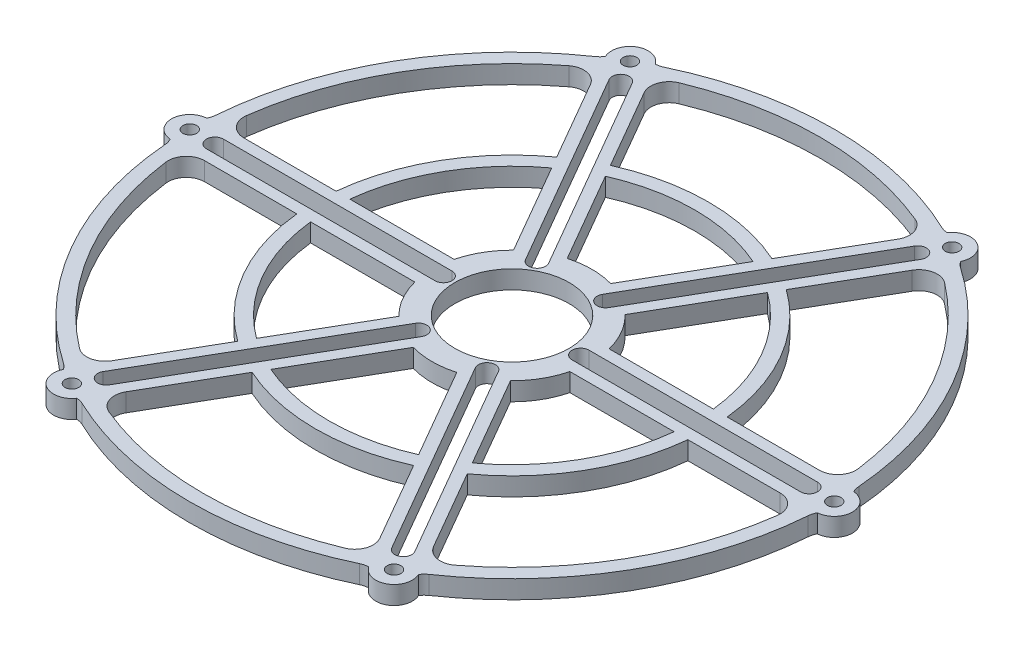
SolidWorks part; units mm, degrees
ref_plane "前视基准面" through (0, 0, 0) normal (0, 0, 1) x (1, 0, 0)
ref_plane "上视基准面" through (0, 0, 0) normal (0, 1, 0) x (1, 0, 0)
ref_plane "右视基准面" through (0, 0, 0) normal (1, 0, 0) x (0, 0, -1)
sketch "草图1" plane through (0, 0, 0) normal (0, 1, 0) x (1, 0, 0)
  line L12 (-35.25, -61.0548) -> (0, 0) construction
  line L13 (-67.3629, 4.3002) -> (-9.579, 4.3002)
  line L14 (-67.3629, -4.3002) -> (-9.579, -4.3002)
  line L15 (9.579, 4.3002) -> (67.3629, 4.3002)
  line L16 (9.579, -4.3002) -> (67.3629, -4.3002)
  line L17 (1.0654, -10.4458) -> (29.9573, -60.4881)
  line L18 (8.5136, -6.1456) -> (37.4056, -56.1878)
  line L19 (-29.9573, 60.4881) -> (-1.0654, 10.4458)
  line L20 (-37.4056, 56.1878) -> (-8.5136, 6.1456)
  line L21 (-8.5136, -6.1456) -> (-37.4056, -56.1878)
  line L22 (-1.0654, -10.4458) -> (-29.9573, -60.4881)
  line L23 (37.4056, 56.1878) -> (8.5136, 6.1456)
  line L24 (29.9573, 60.4881) -> (1.0654, 10.4458)
  line L25 (-9.579, 4.3002) -> (-67.3629, 4.3002)
  line L26 (-9.579, -4.3002) -> (-67.3629, -4.3002)
  line L27 (67.3629, -4.3002) -> (9.579, -4.3002)
  line L28 (67.3629, 4.3002) -> (9.579, 4.3002)
  line L29 (-1.0654, 10.4458) -> (-29.9573, 60.4881)
  line L30 (-8.5136, 6.1456) -> (-37.4056, 56.1878)
  line L31 (29.9573, -60.4881) -> (1.0654, -10.4458)
  line L32 (37.4056, -56.1878) -> (8.5136, -6.1456)
  line L33 (8.5136, 6.1456) -> (37.4056, 56.1878)
  line L34 (1.0654, 10.4458) -> (29.9573, 60.4881)
  line L35 (-37.4056, -56.1878) -> (-8.5136, -6.1456)
  line L36 (-29.9573, -60.4881) -> (-1.0654, -10.4458)
  line L37 (10.5, 0) -> (70.5, 0) construction
  line L38 (-10.5, 0) -> (9.5, 0) construction
  arc A0 (-7.8594, 1.4934) -> (-7.8594, -1.4934) centre (0, 0) ccw construction
  circle A1 centre (-8, 0) radius 1.5
  circle A2 centre (0, 8) radius 1.5
  circle A3 centre (8, 0) radius 1.5
  circle A4 centre (0, -8) radius 1.5
  arc A5 (-8.5136, 6.1456) -> (-9.579, 4.3002) centre (0, 0) ccw
  arc A6 (-67.3629, -4.3002) -> (-37.4056, -56.1878) centre (0, 0) ccw
  arc A7 (-70.5, 3) -> (-70.5, -3) centre (-70.5, 0) ccw
  circle A8 centre (-70.5, 0) radius 1.5
  arc A9 (-32.6519, 62.5548) -> (-37.8481, 59.5548) centre (-35.25, 61.0548) ccw
  circle A10 centre (-35.25, 61.0548) radius 1.5
  arc A11 (37.8481, 59.5548) -> (32.6519, 62.5548) centre (35.25, 61.0548) ccw
  circle A12 centre (35.25, 61.0548) radius 1.5
  arc A13 (70.5, -3) -> (70.5, 3) centre (70.5, 0) ccw
  circle A14 centre (70.5, 0) radius 1.5
  arc A15 (32.6519, -62.5548) -> (37.8481, -59.5548) centre (35.25, -61.0548) ccw
  circle A16 centre (35.25, -61.0548) radius 1.5
  arc A17 (-37.8481, -59.5548) -> (-32.6519, -62.5548) centre (-35.25, -61.0548) ccw
  circle A18 centre (-35.25, -61.0548) radius 1.5
  arc A21 (1.4934, 7.8594) -> (-6.746, 4.3002) centre (0, 0) ccw construction
  arc A22 (-1.4934, -7.8594) -> (1.4934, -7.8594) centre (0, 0) ccw construction
  arc A23 (7.8594, -1.4934) -> (6.746, 4.3002) centre (0, 0) ccw construction
  circle A24 centre (0, 0) radius 4.5
  arc A25 (1.0654, 10.4458) -> (-1.0654, 10.4458) centre (0, 0) ccw
  arc A26 (9.579, 4.3002) -> (8.5136, 6.1456) centre (0, 0) ccw
  arc A27 (8.5136, -6.1456) -> (9.579, -4.3002) centre (0, 0) ccw
  arc A28 (-1.0654, -10.4458) -> (1.0654, -10.4458) centre (0, 0) ccw
  arc A29 (-9.579, -4.3002) -> (-8.5136, -6.1456) centre (0, 0) ccw
  arc A30 (-37.4056, 56.1878) -> (-67.3629, 4.3002) centre (0, 0) ccw
  arc A31 (29.9573, 60.4881) -> (-29.9573, 60.4881) centre (0, 0) ccw
  arc A32 (67.3629, 4.3002) -> (37.4056, 56.1878) centre (0, 0) ccw
  arc A33 (37.4056, -56.1878) -> (67.3629, -4.3002) centre (0, 0) ccw
  arc A34 (-29.9573, -60.4881) -> (29.9573, -60.4881) centre (0, 0) ccw
  arc A35 (32.6519, 62.5548) -> (-32.6519, 62.5548) centre (0, 0) ccw
  arc A36 (70.5, 3) -> (37.8481, 59.5548) centre (0, 0) ccw
  arc A37 (37.8481, -59.5548) -> (70.5, -3) centre (0, 0) ccw
  arc A38 (-32.6519, -62.5548) -> (32.6519, -62.5548) centre (0, 0) ccw
  arc A39 (-70.5, -3) -> (-37.8481, -59.5548) centre (0, 0) ccw
  arc A40 (-37.8481, 59.5548) -> (-70.5, 3) centre (0, 0) ccw
  point P14 (0, 0)
  point P15 (0, 0)
  point P52 (0, 0)
  point P111 (0, 0)
  point P135 (0, 0)
  dimension "D1" = 16
  dimension "D2" = 3
  dimension "D4" = 2.5
  dimension "D5" = 135
  dimension "D6" = 6
  dimension "D7" = 3
  dimension "D9" = 9
  dimension "D8" = 6
  dimension "D3" = 4
  dimension "D10" = 6
extrude "凸台-拉伸1" add sketch "草图1" along normal blind 4 contours A9 A40 A7 A39 A17 A38 A15 A37 A13 A36 A11 A35 L14 A29 L21 A6 A1 A2 region at (-59.3453, 0, -34.263)
fillet "圆角1" radius 4 24 edges at (-37.4056, 2, 56.1878) (-67.3629, 2, 4.3002) (-70.5, 2, 3) (-70.5, 2, -3) (-67.3629, 2, -4.3002) (-37.4056, 2, -56.1878) (-29.9573, 2, -60.4881) (-37.8481, 2, -59.5548) (-32.6519, 2, -62.5548) (32.6519, 2, -62.5548) (29.9573, 2, -60.4881) (37.4056, 2, -56.1878) (37.8481, 2, -59.5548) (70.5, 2, -3) (70.5, 2, 3) (67.3629, 2, -4.3002) (67.3629, 2, 4.3002) (37.8481, 2, 59.5548) (37.4056, 2, 56.1878) (32.6519, 2, 62.5548) (29.9573, 2, 60.4881) (-37.8481, 2, 59.5548) (-29.9573, 2, 60.4881) (-32.6519, 2, 62.5548)
fillet "圆角2" radius 4 12 edges at (-1.0654, 2, 10.4458) (-8.5136, 2, 6.1456) (-9.579, 2, 4.3002) (-9.579, 2, -4.3002) (-8.5136, 2, -6.1456) (1.0654, 2, -10.4458) (-1.0654, 2, -10.4458) (9.579, 2, -4.3002) (8.5136, 2, -6.1456) (9.579, 2, 4.3002) (8.5136, 2, 6.1456) (1.0654, 2, 10.4458)
sketch "草图2" plane through (0, 0, 0) normal (0, -1, 0) x (-1, 0, 0)
  line L0 (23.0864, -63.4293) -> (23.5994, -64.8388)
  line L1 (0, 0) -> (0, -46.6688) construction
  line L2 (-23.0864, -63.4293) -> (-23.5994, -64.8388)
  line L3 (-43.3882, -51.708) -> (-44.3523, -52.8571)
  line L4 (-66.4745, -11.7213) -> (-67.9517, -11.9817)
  line L5 (-66.4745, 11.7213) -> (-67.9517, 11.9817)
  line L6 (-43.3882, 51.708) -> (-44.3523, 52.8571)
  line L7 (-23.0864, 63.4293) -> (-23.5994, 64.8388)
  line L8 (23.0864, 63.4293) -> (23.5994, 64.8388)
  line L9 (43.3882, 51.708) -> (44.3523, 52.8571)
  line L10 (66.4745, 11.7213) -> (67.9517, 11.9817)
  line L11 (66.4745, -11.7213) -> (67.9517, -11.9817)
  line L12 (43.3882, -51.708) -> (44.3523, -52.8571)
  arc A0 (-23.0864, -63.4293) -> (23.0864, -63.4293) centre (0, 0) ccw
  arc A1 (-23.5994, -64.8388) -> (23.5994, -64.8388) centre (0, 0) ccw
  arc A2 (-66.4745, -11.7213) -> (-43.3882, -51.708) centre (0, 0) ccw
  arc A3 (-67.9517, -11.9817) -> (-44.3523, -52.8571) centre (0, 0) ccw
  arc A4 (-43.3882, 51.708) -> (-66.4745, 11.7213) centre (0, 0) ccw
  arc A5 (-44.3523, 52.8571) -> (-67.9517, 11.9817) centre (0, 0) ccw
  arc A6 (23.0864, 63.4293) -> (-23.0864, 63.4293) centre (0, 0) ccw
  arc A7 (23.5994, 64.8388) -> (-23.5994, 64.8388) centre (0, 0) ccw
  arc A8 (66.4745, 11.7213) -> (43.3882, 51.708) centre (0, 0) ccw
  arc A9 (67.9517, 11.9817) -> (44.3523, 52.8571) centre (0, 0) ccw
  arc A10 (43.3882, -51.708) -> (66.4745, -11.7213) centre (0, 0) ccw
  arc A11 (44.3523, -52.8571) -> (67.9517, -11.9817) centre (0, 0) ccw
  point P30 (0, 0)
  dimension "D1" = 1.5
  dimension "D2" = 20
  dimension "D3" = 6
extrude "凸台-拉伸2" add sketch "草图2" along normal blind 5 and the other way blind 9
chamfer "倒角1" distance 0.5 angle 45 6 edges at (59.7558, -5, -34.5) (59.7558, -5, 34.5) (0, -5, 69) (-59.7558, -5, 34.5) (-59.7558, -5, -34.5) (0, -5, -69)
sketch "草图3" plane through (0, 4, 0) normal (0, 1, 0) x (1, 0, 0)
  circle A0 centre (0, 0) radius 40
  circle A1 centre (0, 0) radius 43
  dimension "D1" = 80
  dimension "D2" = 3
extrude "凸台-拉伸3" add sketch "草图3" against normal up to surface (4 mm away) up to face at (-42.1051, 0, 24.3094)
sketch "草图4" plane through (0, 4, 0) normal (0, 1, 0) x (1, 0, 0)
  circle A0 centre (0, 0) radius 12.5
  dimension "D1" = 25
extrude "切除-拉伸1" cut sketch "草图4" against normal blind 10
sketch "草图5" plane through (0, 4, 0) normal (0, 1, 0) x (1, 0, 0)
  circle A0 centre (0, 0) radius 12.5
  circle A1 centre (0, 0) radius 17.5
  dimension "D1" = 5
extrude "凸台-拉伸4" add sketch "草图5" against normal up to surface (4 mm away) up to face at (0, 0, 58.1881)
sketch "草图7" plane through (0, 0, 0) normal (0, -1, 0) x (-1, 0, 0)
  circle A0 centre (0, 0) radius 99.6246
extrude "切除-拉伸3" cut sketch "草图7" along normal blind 33
sketch "草图8" plane through (0, 4, 0) normal (0, 1, 0) x (1, 0, 0)
  circle A0 centre (0, 0) radius 104.7007
extrude "切除-拉伸4" cut sketch "草图8" along normal blind 205
sketch "草图9" plane through (0, 0, 0) normal (0, -1, 0) x (-1, 0, 0)
  circle A0 centre (35.25, 61.0548) radius 4
  circle A1 centre (70.5, 0) radius 4
  circle A2 centre (35.25, -61.0548) radius 4
  circle A3 centre (-35.25, -61.0548) radius 4
  circle A4 centre (-70.5, 0) radius 4
  circle A5 centre (-35.25, 61.0548) radius 4
  circle A6 centre (35.25, 61.0548) radius 1.5
  circle A7 centre (70.5, 0) radius 1.5
  circle A8 centre (35.25, -61.0548) radius 1.5
  circle A9 centre (-35.25, -61.0548) radius 1.5
  circle A10 centre (-70.5, 0) radius 1.5
  circle A11 centre (-35.25, 61.0548) radius 1.5
  point P15 (0, 0)
  point P27 (0, 0)
  dimension "D1" = 8
  dimension "D2" = 6
  dimension "D3" = 6
extrude "凸台-拉伸5" add sketch "草图9" against normal up to surface (4 mm away) up to face at (0, 4, 27.7328)
sketch "草图10" plane through (0, 4, 0) normal (0, 1, 0) x (1, 0, 0)
  line L0 (-65, 0) -> (-15, 0) construction
  line L1 (-65, 1.8514) -> (-15, 1.8514)
  line L2 (-65, -1.8514) -> (-15, -1.8514)
  line L3 (-32.5, 56.2917) -> (-7.5, 12.9904) construction
  line L4 (-30.8966, 57.2174) -> (-5.8966, 13.9161)
  line L5 (-34.1034, 55.3659) -> (-9.1034, 12.0647)
  line L6 (32.5, 56.2917) -> (7.5, 12.9904) construction
  line L7 (34.1034, 55.3659) -> (9.1034, 12.0647)
  line L8 (30.8966, 57.2174) -> (5.8966, 13.9161)
  line L9 (65, 0) -> (15, 0) construction
  line L10 (65, -1.8514) -> (15, -1.8514)
  line L11 (65, 1.8514) -> (15, 1.8514)
  line L12 (32.5, -56.2917) -> (7.5, -12.9904) construction
  line L13 (30.8966, -57.2174) -> (5.8966, -13.9161)
  line L14 (34.1034, -55.3659) -> (9.1034, -12.0647)
  line L15 (-32.5, -56.2917) -> (-7.5, -12.9904) construction
  line L16 (-34.1034, -55.3659) -> (-9.1034, -12.0647)
  line L17 (-30.8966, -57.2174) -> (-5.8966, -13.9161)
  arc A0 (-65, 1.8514) -> (-65, -1.8514) centre (-65, 0) ccw
  arc A1 (-15, -1.8514) -> (-15, 1.8514) centre (-15, 0) ccw
  arc A2 (-30.8966, 57.2174) -> (-34.1034, 55.3659) centre (-32.5, 56.2917) ccw
  arc A3 (-9.1034, 12.0647) -> (-5.8966, 13.9161) centre (-7.5, 12.9904) ccw
  arc A4 (34.1034, 55.3659) -> (30.8966, 57.2174) centre (32.5, 56.2917) ccw
  arc A5 (5.8966, 13.9161) -> (9.1034, 12.0647) centre (7.5, 12.9904) ccw
  arc A6 (65, -1.8514) -> (65, 1.8514) centre (65, 0) ccw
  arc A7 (15, 1.8514) -> (15, -1.8514) centre (15, 0) ccw
  arc A8 (30.8966, -57.2174) -> (34.1034, -55.3659) centre (32.5, -56.2917) ccw
  arc A9 (9.1034, -12.0647) -> (5.8966, -13.9161) centre (7.5, -12.9904) ccw
  arc A10 (-34.1034, -55.3659) -> (-30.8966, -57.2174) centre (-32.5, -56.2917) ccw
  arc A11 (-5.8966, -13.9161) -> (-9.1034, -12.0647) centre (-7.5, -12.9904) ccw
  point P3 (-40, 0)
  point P13 (-20, 34.641)
  point P20 (20, 34.641)
  point P27 (40, 0)
  point P34 (20, -34.641)
  point P41 (-20, -34.641)
  point P46 (0, 0)
  dimension "D1" = 50
  dimension "D2" = 40
  dimension "D3" = 6
extrude "切除-拉伸5" cut sketch "草图10" against normal blind 10 contours L2 A1 L1 A0 | L4 A3 L5 A2 | L7 A5 L8 A4 | L13 A9 L14 A8 | L16 A11 L17 A10 | L10 A7 L11 A6
